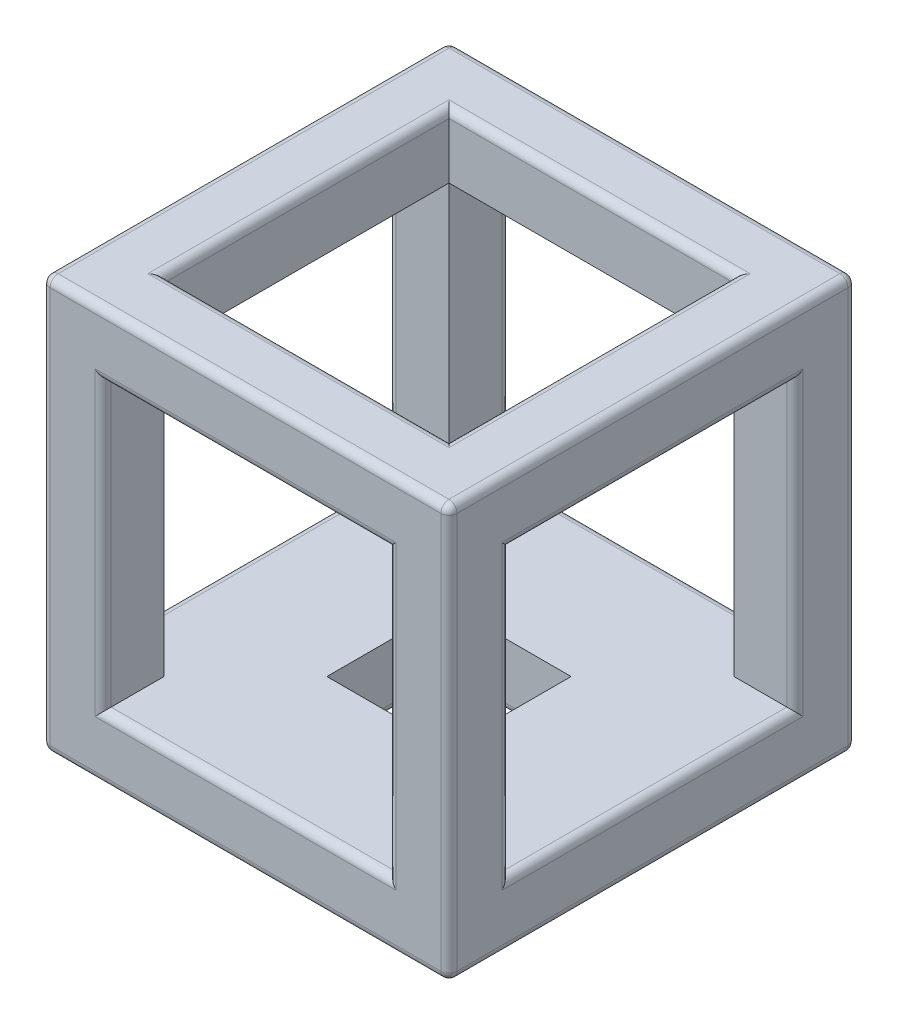
SolidWorks part; units mm, degrees
ref_plane "Front Plane" through (0, 0, 0) normal (0, 0, 1) x (1, 0, 0)
ref_plane "Top Plane" through (0, 0, 0) normal (0, 1, 0) x (1, 0, 0)
ref_plane "Right Plane" through (0, 0, 0) normal (1, 0, 0) x (0, 0, -1)
sketch "Sketch1" plane through (0, 0, 0) normal (0, 1, 0) x (1, 0, 0)
  line L1 (61.6445, 48.0373) -> (-65.3555, 48.0373)
  line L2 (61.6445, 48.0373) -> (61.6445, -78.9627)
  line L3 (61.6445, -78.9627) -> (-65.3555, -78.9627)
  line L4 (-65.3555, 48.0373) -> (-65.3555, -78.9627)
  line L5 (61.6445, 48.0373) -> (-65.3555, -78.9627) construction
  line L6 (61.6445, -78.9627) -> (-65.3555, 48.0373) construction
  point P0 (-1.8555, -15.4627)
  dimension "D1" = 127
  dimension "D2" = 127
extrude "Boss-Extrude1" add sketch "Sketch1" along normal blind 128.778 contours L2 L1 L4 L3
sketch "Sketch2" plane through (0, 0, 78.9627) normal (0, 0, 1) x (1, 0, 0)
  line L0 (-65.3555, 64.389) -> (61.6445, 64.389) construction
  line L1 (-46.3055, 19.939) -> (42.5945, 19.939)
  line L2 (-46.3055, 19.939) -> (-46.3055, 108.839)
  line L3 (-46.3055, 108.839) -> (42.5945, 108.839)
  line L4 (42.5945, 19.939) -> (42.5945, 108.839)
  line L5 (-46.3055, 19.939) -> (42.5945, 108.839) construction
  line L6 (-46.3055, 108.839) -> (42.5945, 19.939) construction
  line L7 (-65.3555, 128.778) -> (-65.3555, 0) construction
  line L8 (61.6445, 128.778) -> (61.6445, 0) construction
  line L9 (-1.8555, 128.778) -> (-1.8555, 0) construction
  line L10 (61.6445, 128.778) -> (-65.3555, 128.778) construction
  point P0 (-1.8555, 64.389)
  dimension "D1" = 88.9
  dimension "D2" = 88.9
extrude "Cut-Extrude1" cut sketch "Sketch2" against normal through all contours L3 L4 L1 L2
sketch "Sketch4" plane through (61.6445, 0, 0) normal (1, 0, 0) x (0, 0, -1)
  line L0 (-78.9627, 64.389) -> (48.0373, 64.389) construction
  line L1 (-59.9127, 19.939) -> (28.9873, 19.939)
  line L2 (-59.9127, 19.939) -> (-59.9127, 108.839)
  line L4 (28.9873, 19.939) -> (28.9873, 108.839)
  line L5 (-59.9127, 19.939) -> (28.9873, 108.839) construction
  line L6 (-59.9127, 108.839) -> (28.9873, 19.939) construction
  line L7 (-78.9627, 128.778) -> (-78.9627, 0) construction
  line L8 (48.0373, 128.778) -> (48.0373, 0) construction
  line L9 (-15.4627, 128.778) -> (-15.4627, 0) construction
  line L10 (48.0373, 128.778) -> (-78.9627, 128.778) construction
  line L11 (48.0373, 0) -> (-78.9627, 0) construction
  line L12 (-59.9127, 108.839) -> (28.9873, 108.839)
  point P0 (-15.4627, 64.389)
  dimension "D1" = 88.9
  dimension "D2" = 88.9
extrude "Cut-Extrude4" cut sketch "Sketch4" against normal through all
sketch "Sketch6" plane through (0, 0, 0) normal (0, -1, 0) x (1, 0, 0)
  line L0 (-65.3555, 15.4627) -> (61.6445, 15.4627) construction
  line L1 (-20.9055, -3.5873) -> (17.1945, -3.5873)
  line L2 (-20.9055, -3.5873) -> (-20.9055, 34.5127)
  line L3 (-20.9055, 34.5127) -> (17.1945, 34.5127)
  line L4 (17.1945, -3.5873) -> (17.1945, 34.5127)
  line L5 (-20.9055, -3.5873) -> (17.1945, 34.5127) construction
  line L6 (-20.9055, 34.5127) -> (17.1945, -3.5873) construction
  line L7 (-65.3555, -48.0373) -> (-65.3555, 78.9627) construction
  line L8 (61.6445, -48.0373) -> (61.6445, 78.9627) construction
  point P0 (-1.8555, 15.4627)
  dimension "D1" = 38.1
  dimension "D2" = 38.1
extrude "Cut-Extrude5" cut sketch "Sketch6" against normal up to next contours L2 L1 L4 L3
sketch "Sketch7" plane through (0, 128.778, 0) normal (0, 1, 0) x (1, 0, 0)
  line L0 (-65.3555, -15.4627) -> (61.6445, -15.4627) construction
  line L1 (-46.3055, -59.9127) -> (42.5945, -59.9127)
  line L2 (-46.3055, -59.9127) -> (-46.3055, 28.9873)
  line L3 (-46.3055, 28.9873) -> (42.5945, 28.9873)
  line L4 (42.5945, -59.9127) -> (42.5945, 28.9873)
  line L5 (-46.3055, -59.9127) -> (42.5945, 28.9873) construction
  line L6 (-46.3055, 28.9873) -> (42.5945, -59.9127) construction
  line L7 (-65.3555, 48.0373) -> (-65.3555, -78.9627) construction
  line L8 (61.6445, 48.0373) -> (61.6445, -78.9627) construction
  line L9 (-1.8555, 48.0373) -> (-1.8555, -78.9627) construction
  line L12 (61.6445, 48.0373) -> (-65.3555, 48.0373) construction
  line L13 (61.6445, -78.9627) -> (-65.3555, -78.9627) construction
  point P0 (-1.8555, -15.4627)
  dimension "D1" = 88.9
  dimension "D2" = 88.9
extrude "Cut-Extrude6" cut sketch "Sketch7" against normal up to next contours L2 L1 L4 L3
fillet "Fillet1" radius 2.54 1 edges at (61.6445, 64.389, 78.9627)
fillet "Fillet2" radius 2.54 14 edges at (60.9005, 0, 78.2187) (42.5945, 128.778, 15.4627) (-1.8555, 128.778, -28.9873) (-46.3055, 128.778, 15.4627) (-1.8555, 128.778, 59.9127) (-65.3555, 128.778, 15.4627) (-1.8555, 128.778, -48.0373) (61.6445, 128.778, 14.1927) (60.9005, 128.778, 78.2187) (-3.1255, 128.778, 78.9627) (61.6445, 64.389, -48.0373) (-65.3555, 64.389, 78.9627) (-3.1255, 0, 78.9627) (61.6445, 0, 14.1927)
fillet "Fillet3" radius 2.54 6 edges at (-64.6116, 0.7439, 78.2187) (-64.6116, 128.0341, -47.2934) (60.9005, 0.7439, -47.2934) (-65.3555, 0, 14.1927) (-65.3555, 63.119, -48.0373) (-3.1255, 0, -48.0373)
fillet "Fillet4" radius 2.54 4 edges at (17.1945, 0, 15.4627) (-1.8555, 0, -3.5873) (-1.8555, 0, 34.5127) (-20.9055, 0, 15.4627)
fillet "Fillet5" radius 2.54 2 edges at (-46.3055, 64.389, 78.9627) (-46.3055, 64.389, -48.0373)
fillet "Fillet6" radius 2.54 3 edges at (-3.1255, 108.839, -48.0373) (42.5945, 64.389, -48.0373) (-3.1255, 19.939, -48.0373)
fillet "Fillet7" radius 2.54 4 edges at (-65.3555, 19.939, 15.4627) (-65.3555, 64.389, 59.9127) (-65.3555, 108.839, 15.4627) (-65.3555, 64.389, -28.9873)
fillet "Fillet8" radius 2.54 3 edges at (-3.1255, 19.939, 78.9627) (42.5945, 64.389, 78.9627) (-3.1255, 108.839, 78.9627)
fillet "Fillet9" radius 2.54 4 edges at (61.6445, 64.389, 59.9127) (61.6445, 19.939, 15.4627) (61.6445, 64.389, -28.9873) (61.6445, 108.839, 15.4627)
